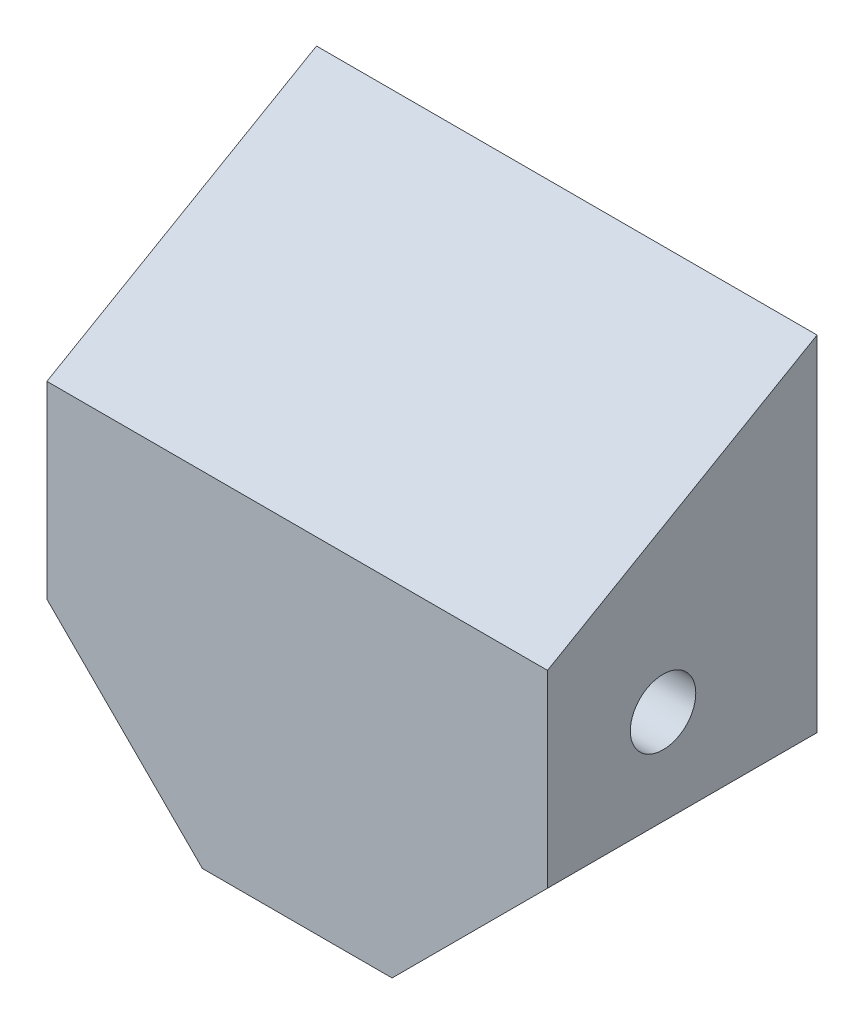
SolidWorks part; units mm, degrees
material "Silicon Rubber"
ref_plane "Front Plane" through (0, 0, 0) normal (0, 0, 1) x (1, 0, 0)
ref_plane "Top Plane" through (0, 0, 0) normal (0, 1, 0) x (1, 0, 0)
ref_plane "Right Plane" through (0, 0, 0) normal (1, 0, 0) x (0, 0, -1)
sketch "Sketch2" plane through (0, 0, 0) normal (0, 0, 1) x (1, 0, 0)
  line L1 (-165.1, -165.1) -> (165.1, -165.1)
  line L2 (-165.1, -165.1) -> (-165.1, 165.1)
  line L3 (-165.1, 165.1) -> (165.1, 165.1)
  line L4 (165.1, -165.1) -> (165.1, 165.1)
  line L5 (-165.1, -165.1) -> (165.1, 165.1) construction
  line L6 (-165.1, 165.1) -> (165.1, -165.1) construction
  point P0 (0, 0)
extrude "Boss-Extrude1" add sketch "Sketch2" along normal blind 177.8
sketch "Sketch3" plane through (165.1, 0, 0) normal (1, 0, 0) x (0, 0, -1)
  circle A0 centre (-101.6, 0) radius 21.59
extrude "Cut-Extrude1" cut sketch "Sketch3" against normal through all both and the other way through all
sketch "Sketch5" plane through (0, 0, 0) normal (0, 0, -1) x (-1, 0, 0)
  circle A0 centre (0, 0) radius 8.382
extrude "Cut-Extrude3" cut sketch "Sketch5" against normal blind 101.6
sketch "Sketch6" plane through (0, -165.1, 0) normal (0, -1, 0) x (1, 0, 0)
  circle A0 centre (0, 101.6) radius 21.59
extrude "Cut-Extrude4" cut sketch "Sketch6" against normal blind 165.1
fillet "Fillet1" [suppressed] radius 5.08
fillet "Fillet2" [suppressed] radius 25.4
chamfer "Chamfer3" [suppressed] distance 77.14 angle 45 tangent propagation no
chamfer "Chamfer4" [suppressed] distance 77.14 angle 45 tangent propagation no
chamfer "Chamfer5" [suppressed] distance 26.34 angle 70
chamfer "Chamfer6" distance 178.74 angle 30 1 edges at (0, 165.1, 177.8) first distance on face at (0, 165.1, 88.9)
chamfer "Chamfer7" distance 102.54 angle 45 2 edges at (165.1, -165.1, 88.9) (-165.1, -165.1, 88.9)
